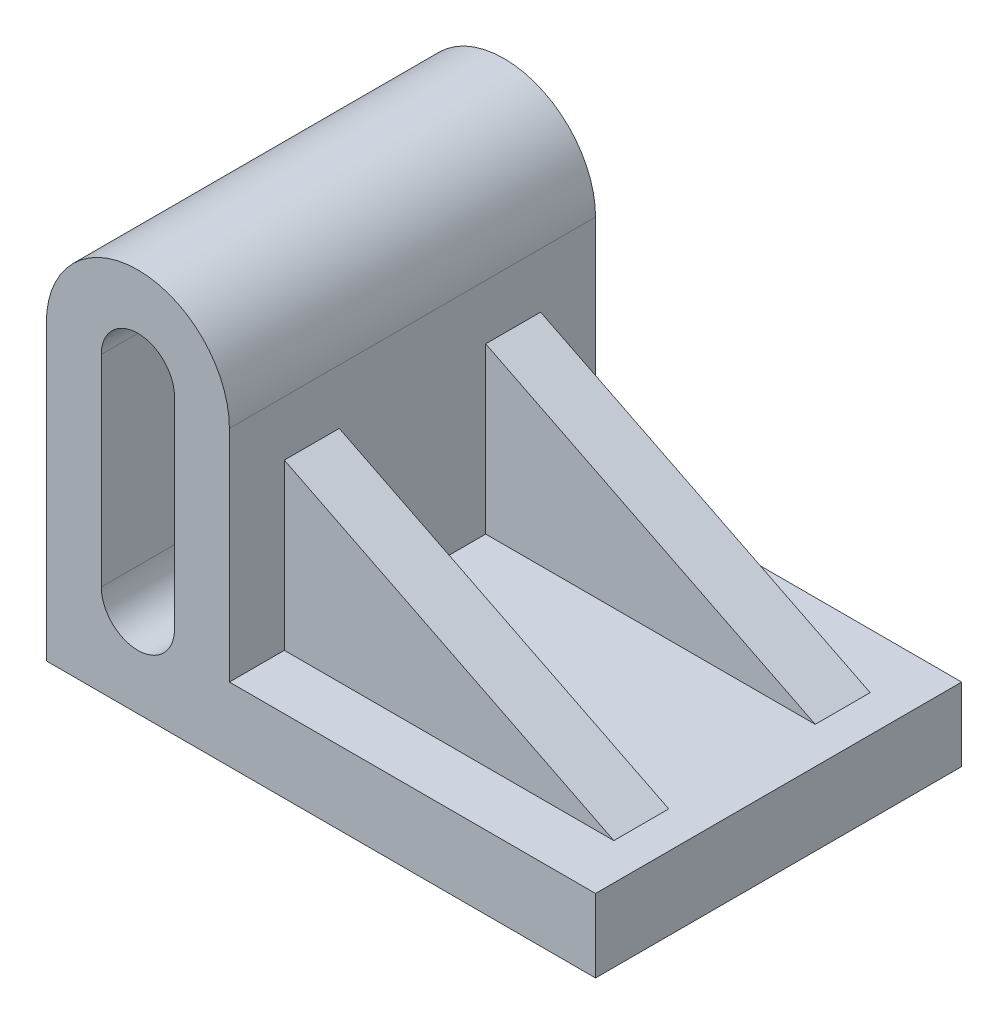
SolidWorks part; units mm, degrees
ref_plane "Front Plane" through (0, 0, 0) normal (0, 0, 1) x (1, 0, 0)
ref_plane "Top Plane" through (0, 0, 0) normal (0, 1, 0) x (1, 0, 0)
ref_plane "Right Plane" through (0, 0, 0) normal (1, 0, 0) x (0, 0, -1)
sketch "Sketch1" plane through (0, 0, 0) normal (0, 0, 1) x (1, 0, 0)
  line L0 (0, 0) -> (150, 0)
  line L1 (150, 0) -> (150, 20)
  line L2 (150, 20) -> (50, 20)
  line L3 (50, 20) -> (50, 80)
  line L5 (0, 80) -> (0, 0)
  arc A0 (50, 80) -> (0, 80) centre (25, 80) ccw
  point P9 (23.1039, 120.651)
  point P10 (0, 0)
  dimension "D4" = 50
  dimension "D1" = 150
  dimension "D2" = 20
  dimension "D3" = 80
extrude "Boss-Extrude1" add sketch "Sketch1" along normal blind 50 and the other way blind 50
sketch "Sketch3" plane through (0, 0, 0) normal (0, 0, 1) x (1, 0, 0)
  line L0 (25, 80) -> (25, 25) construction
  line L1 (35, 80) -> (35, 25)
  line L2 (15, 80) -> (15, 25)
  line L3 (50, 20) -> (50, 80) construction
  arc A0 (35, 80) -> (15, 80) centre (25, 80) ccw
  arc A1 (15, 25) -> (35, 25) centre (25, 25) ccw
  point P2 (25, 52.5)
  dimension "D2" = 10
  dimension "D1" = 55
  dimension "D3" = 25
  dimension "D4" = 15
extrude "Cut-Extrude1" cut sketch "Sketch3" against normal through all and the other way through all
sketch "Sketch4" plane through (0, 0, 0) normal (0, 0, 1) x (1, 0, 0)
  line L0 (50, 65) -> (50, 20)
  line L1 (50, 20) -> (50, 80) construction
  line L2 (50, 20) -> (140, 20)
  line L3 (150, 20) -> (50, 20) construction
  line L4 (140, 20) -> (50, 65)
  point P4 (140, 20)
  dimension "D1" = 45
  dimension "D2" = 10
extrude "Boss-Extrude2" add sketch "Sketch4" along normal blind 35 and the other way blind 35
sketch "Sketch5" plane through (0, 0, 0) normal (0, 0, 1) x (1, 0, 0)
  line L0 (50, 65) -> (50, 20)
  line L1 (50, 20) -> (140, 20)
  line L2 (140, 20) -> (50, 65)
  line L3 (50, 65) -> (50, 20) construction
  line L4 (50, 20) -> (140, 20) construction
extrude "Cut-Extrude2" cut sketch "Sketch5" against normal blind 20 and the other way blind 20
